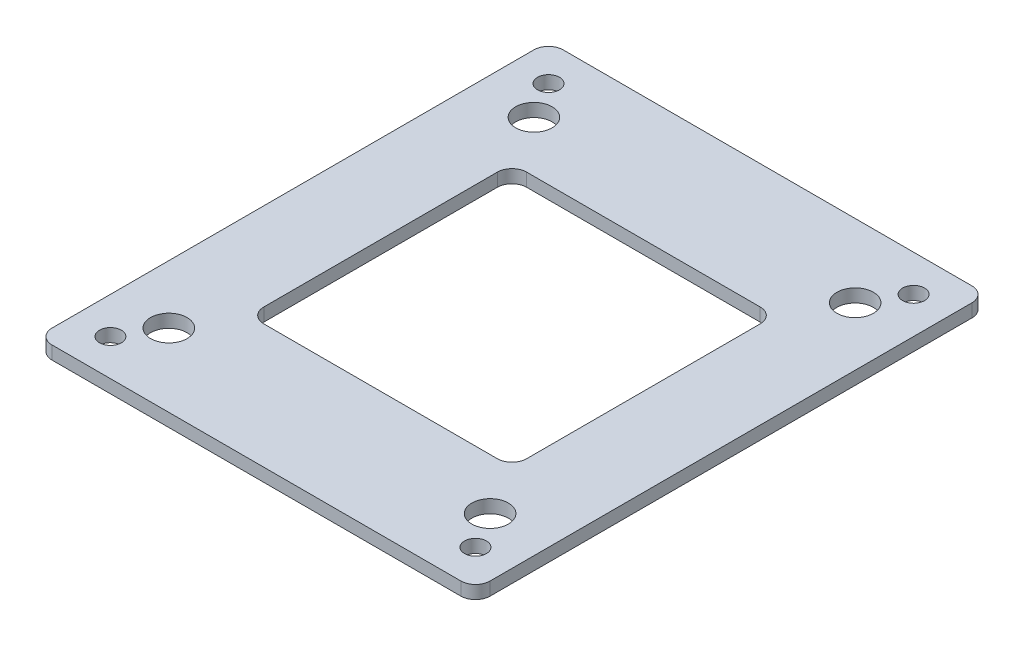
SolidWorks part; units mm, degrees
ref_plane "前视基准面" through (0, 0, 0) normal (0, 0, 1) x (1, 0, 0)
ref_plane "上视基准面" through (0, 0, 0) normal (0, 1, 0) x (1, 0, 0)
ref_plane "右视基准面" through (0, 0, 0) normal (1, 0, 0) x (0, 0, -1)
other "Configuration Table"
sketch "草图1" plane through (0, 0, 0) normal (0, 1, 0) x (1, 0, 0)
  line L1 (-30, -35) -> (30, -35)
  line L2 (-30, -35) -> (-30, 35)
  line L3 (-30, 35) -> (30, 35)
  line L4 (30, -35) -> (30, 35)
  line L5 (0, 35) -> (0, -35) construction
  line L6 (-30, 0) -> (30, 0) construction
  circle A0 centre (-22, 25) radius 2.5
  circle A1 centre (22, 25) radius 2.5
  circle A2 centre (22, -25) radius 2.5
  circle A3 centre (-22, -25) radius 2.5
  point P0 (0, 0)
  dimension "D3" = 5
  dimension "D4" = 25
  dimension "D5" = 22
  dimension "D1" = 60
  dimension "D2" = 70
extrude "凸台-拉伸1" add sketch "草图1" along normal blind 1.8
sketch "草图2" plane through (0, 1.8, 0) normal (0, 1, 0) x (1, 0, 0)
  line L0 (-1000, 0) -> (49000, 0) construction
  line L1 (0, -1000) -> (0, 49000) construction
  line L3 (-18, -18) -> (18, -18)
  line L4 (-18, -18) -> (-18, 18)
  line L5 (-18, 18) -> (18, 18)
  line L6 (18, -18) -> (18, 18)
  line L7 (0, 18) -> (0, -18) construction
  line L8 (-18, 0) -> (18, 0) construction
  circle A0 centre (-25, 30) radius 1.5
  circle A1 centre (25, 30) radius 1.5
  circle A2 centre (25, -30) radius 1.5
  circle A3 centre (-25, -30) radius 1.5
  point P13 (0, 0)
  dimension "D1" = 3
  dimension "D2" = 30
  dimension "D3" = 25
  dimension "D4" = 36
  dimension "D5" = 36
extrude "切除-拉伸1" cut sketch "草图2" against normal through all
fillet "圆角1" radius 2 8 edges at (18, 0.9, -18) (-18, 0.9, -18) (18, 0.9, 18) (-18, 0.9, 18) (-30, 0.9, 35) (30, 0.9, 35) (30, 0.9, -35) (-30, 0.9, -35)
